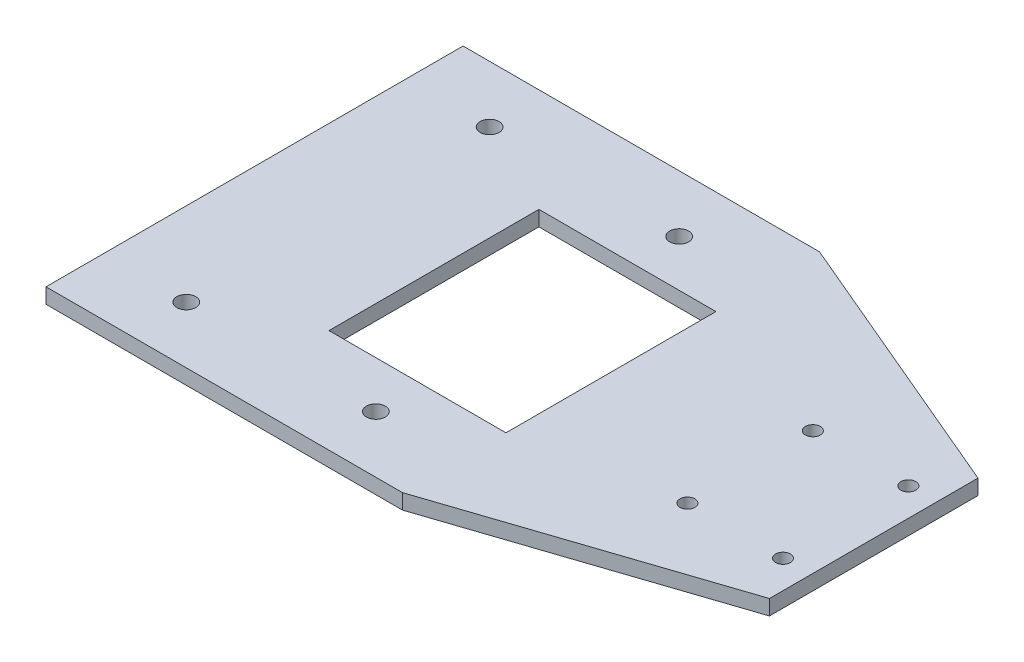
SolidWorks part; units mm, degrees
ref_plane "Front Plane" through (0, 0, 0) normal (0, 0, 1) x (1, 0, 0)
ref_plane "Top Plane" through (0, 0, 0) normal (0, 1, 0) x (1, 0, 0)
ref_plane "Right Plane" through (0, 0, 0) normal (1, 0, 0) x (0, 0, -1)
sketch "Sketch1" plane through (0, 0, 0) normal (0, 1, 0) x (1, 0, 0)
  line L0 (75.945, 15.3764) -> (29.845, 34.925)
  line L1 (-15.875, -25.4) -> (15.875, -25.4) construction
  line L2 (-15.875, -25.4) -> (-15.875, 25.4) construction
  line L3 (-15.875, 25.4) -> (15.875, 25.4) construction
  line L4 (15.875, -25.4) -> (15.875, 25.4) construction
  line L5 (-15.875, -25.4) -> (15.875, 25.4) construction
  line L6 (-15.875, 25.4) -> (15.875, -25.4) construction
  line L7 (29.845, -34.925) -> (-29.845, -34.925)
  line L8 (29.845, -34.925) -> (29.845, 34.925) construction
  line L9 (29.845, 34.925) -> (-29.845, 34.925)
  line L10 (-29.845, -34.925) -> (-29.845, 34.925)
  line L11 (29.845, -34.925) -> (-29.845, 34.925) construction
  line L12 (29.845, 34.925) -> (-29.845, -34.925) construction
  line L13 (55.245, -12.5861) -> (71.245, -12.5861) construction
  line L14 (55.245, -12.5861) -> (55.245, 8.4139) construction
  line L15 (55.245, 8.4139) -> (71.245, 8.4139) construction
  line L16 (71.245, -12.5861) -> (71.245, 8.4139) construction
  line L17 (55.245, -12.5861) -> (71.245, 8.4139) construction
  line L18 (55.245, 8.4139) -> (71.245, -12.5861) construction
  line L19 (50.545, 15.3764) -> (75.945, 15.3764) construction
  line L20 (50.545, 15.3764) -> (50.545, -19.5486) construction
  line L21 (50.545, -19.5486) -> (75.945, -19.5486) construction
  line L22 (75.945, 15.3764) -> (75.945, -19.5486)
  line L23 (50.545, 15.3764) -> (75.945, -19.5486) construction
  line L24 (50.545, -19.5486) -> (75.945, 15.3764) construction
  line L25 (75.945, -19.5486) -> (29.845, -34.925)
  circle A0 centre (-15.875, 25.4) radius 1.5875
  circle A1 centre (15.875, 25.4) radius 1.5875
  circle A2 centre (15.875, -25.4) radius 1.5875
  circle A3 centre (-15.875, -25.4) radius 1.5875
  circle A4 centre (71.245, 8.4139) radius 1.25
  circle A5 centre (71.245, -12.5861) radius 1.25
  circle A6 centre (55.245, -12.5861) radius 1.25
  circle A8 centre (55.245, 8.4139) radius 1.25
  point P0 (0, 0)
  point P7 (0, 0)
  point P15 (63.245, -2.0861)
  point P21 (0, 0)
  point P23 (63.245, -2.0861)
  dimension "D3" = 3.175
  dimension "D8" = 2.5
  dimension "D1" = 50.8
  dimension "D2" = 31.75
  dimension "D4" = 69.85
  dimension "D5" = 13.97
  dimension "D6" = 21
  dimension "D7" = 16
  dimension "D9" = 25.4
  dimension "D10" = 34.925
  dimension "D11" = 25.4
extrude "Boss-Extrude1" add sketch "Sketch1" along normal blind 2.54
sketch "Sketch2" plane through (0, 2.54, 0) normal (0, 1, 0) x (1, 0, 0)
  line L6 (29.845, 17.582) -> (0.2018, 17.582)
  line L8 (29.845, 17.582) -> (29.845, -17.582)
  line L9 (29.845, -17.582) -> (0.2018, -17.582)
  line L10 (0.2018, 17.582) -> (0.2018, -17.582)
  line L11 (29.845, 17.582) -> (0.2018, -17.582) construction
  line L12 (29.845, -17.582) -> (0.2018, 17.582) construction
  point P0 (0, 0)
  point P1 (15.0234, 0)
  point P9 (0, 0)
extrude "Cut-Extrude1" cut sketch "Sketch2" against normal blind 2.54
